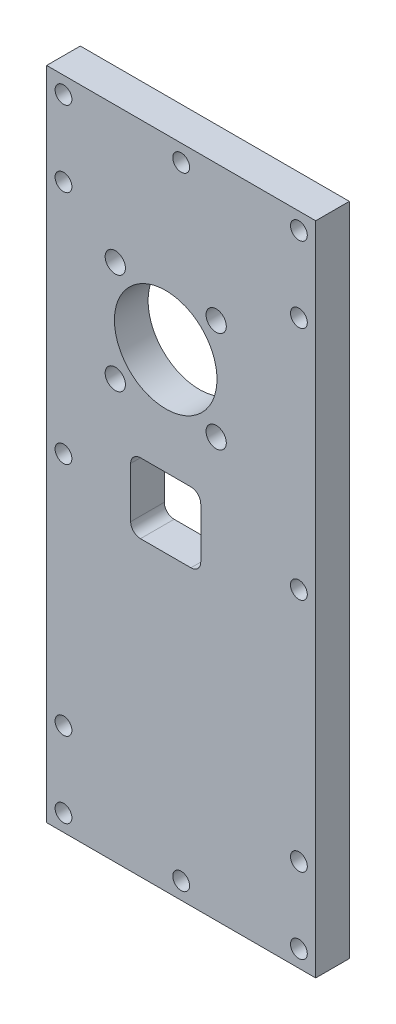
SolidWorks part; units mm, degrees
ref_plane "Ebene vorne" through (0, 0, 0) normal (0, 0, 1) x (1, 0, 0)
ref_plane "Ebene oben" through (0, 0, 0) normal (0, 1, 0) x (1, 0, 0)
ref_plane "Ebene rechts" through (0, 0, 0) normal (1, 0, 0) x (0, 0, -1)
sketch "Skizze1" plane through (0, 0, 0) normal (0, 0, 1) x (1, 0, 0)
  line L1 (-69.0594, 70.0995) -> (10.9406, 70.0995)
  line L2 (-69.0594, 70.0995) -> (-69.0594, -124.9005)
  line L3 (-69.0594, -124.9005) -> (10.9406, -124.9005)
  line L4 (10.9406, 70.0995) -> (10.9406, -124.9005)
  dimension "D1" = 195
  dimension "D2" = 80
extrude "Aufsatz-Linear austragen1" add sketch "Skizze1" against normal blind 10
sketch "Skizze2" plane through (0, 0, -10) normal (0, 0, -1) x (-1, 0, 0)
  line L0 (69.0594, 70.0995) -> (69.0594, -124.9005) construction
  line L1 (33.6594, 14.5995) -> (33.6594, -27.4005) construction
  line L3 (33.6594, 14.5995) -> (69.0594, 14.5995) construction
  line L5 (18.6594, 29.5995) -> (48.6594, 29.5995) construction
  line L6 (48.6594, 29.5995) -> (48.6594, -0.4005) construction
  line L7 (48.6594, -0.4005) -> (18.6594, -0.4005) construction
  line L8 (18.6594, -0.4005) -> (18.6594, 29.5995) construction
  line L9 (18.6594, 29.5995) -> (48.6594, -0.4005) construction
  line L10 (69.0594, -27.4005) -> (-10.9406, -27.4005) construction
  line L11 (-10.9406, -124.9005) -> (-10.9406, 70.0995) construction
  line L12 (23.2413, -19.9005) -> (23.2413, -34.9005)
  line L13 (26.1594, -16.9824) -> (41.1594, -16.9824)
  line L14 (44.0774, -19.9005) -> (44.0774, -34.9005)
  line L15 (41.1594, -37.8185) -> (26.1594, -37.8185)
  line L16 (23.2413, -19.9005) -> (44.0774, -34.9005) construction
  line L17 (26.1594, -37.8185) -> (41.1594, -16.9824) construction
  circle A0 centre (18.6594, 29.5995) radius 3.015
  circle A1 centre (48.6594, 29.5995) radius 3.015
  circle A2 centre (18.6594, -0.4005) radius 3.015
  circle A3 centre (48.6594, -0.4005) radius 3.015
  circle A4 centre (33.6594, 14.5995) radius 15.25
  arc A5 (23.2413, -19.9005) -> (26.1594, -16.9824) centre (26.1594, -19.9005) cw
  arc A6 (41.1594, -16.9824) -> (44.0774, -19.9005) centre (41.1594, -19.9005) cw
  arc A7 (44.0774, -34.9005) -> (41.1594, -37.8185) centre (41.1594, -34.9005) cw
  arc A8 (26.1594, -37.8185) -> (23.2413, -34.9005) centre (26.1594, -34.9005) cw
  point P22 (33.6594, 14.5995)
  point P32 (33.6594, -27.4005)
  dimension "D1" = 30
  dimension "D3" = 6.03
  dimension "D2" = 30
  dimension "D4" = 35.4
  dimension "D5" = 42
  dimension "D6" = 15
extrude "Schnitt-Linear austragen1" cut sketch "Skizze2" against normal blind 10
sketch "Skizze3" plane through (0, 0, -10) normal (0, 0, -1) x (-1, 0, 0)
  line L0 (-5.9406, 65.0995) -> (63.8159, 65.0995) construction
  line L1 (63.8159, 65.0995) -> (63.8159, 42.5995) construction
  line L2 (63.8159, 42.5995) -> (63.8159, -27.4005) construction
  line L4 (63.8159, -27.4005) -> (63.8159, -97.4005) construction
  line L5 (63.8159, -97.4005) -> (63.8159, -119.9005) construction
  line L6 (63.8159, -119.9005) -> (-5.9406, -119.9005) construction
  line L7 (-5.9406, -119.9005) -> (-5.9406, -97.4005) construction
  line L8 (-5.9406, -97.4005) -> (-5.9406, -27.4005) construction
  line L10 (-5.9406, -27.4005) -> (-5.9406, 42.5995) construction
  line L11 (-5.9406, 42.5995) -> (-5.9406, 65.0995) construction
  line L12 (28.9377, 65.0995) -> (29.0594, 70.0995) construction
  line L13 (-10.9406, 70.0995) -> (69.0594, 70.0995) construction
  line L14 (28.9377, -119.9005) -> (29.0594, -124.9005) construction
  line L15 (69.0594, -124.9005) -> (-10.9406, -124.9005) construction
  line L16 (-10.9406, -124.9005) -> (-10.9406, 70.0995) construction
  circle A0 centre (-5.9406, 65.0995) radius 1.25
  circle A1 centre (63.8159, 65.0995) radius 1.25
  circle A2 centre (28.9377, 65.0995) radius 1.25
  circle A3 centre (63.8159, 42.5995) radius 1.25
  circle A5 centre (63.8159, -27.4005) radius 1.25
  circle A6 centre (63.8159, -97.4005) radius 1.25
  circle A7 centre (63.8159, -119.9005) radius 1.25
  circle A8 centre (28.9377, -119.9005) radius 1.25
  circle A9 centre (-5.9406, -119.9005) radius 1.25
  circle A10 centre (-5.9406, -97.4005) radius 1.25
  circle A11 centre (-5.9406, -27.4005) radius 1.25
  circle A13 centre (-5.9406, 42.5995) radius 1.25
  point P26 (-5.9406, -26.6299)
  dimension "D4" = 2.5
  dimension "D1" = 5
  dimension "D2" = 5
  dimension "D3" = 5
  dimension "D5" = 70
extrude "Schnitt-Linear austragen2" cut sketch "Skizze3" against normal blind 5
sketch "Skizze4" plane through (0, 0, 0) normal (0, 0, 1) x (1, 0, 0)
  line L0 (-64.0594, 65.0995) -> (-64.0594, 42.5995) construction
  line L1 (-64.0594, 42.5995) -> (-64.0594, -27.4005) construction
  line L2 (-64.0594, -27.4005) -> (-64.0594, -97.4005) construction
  line L3 (-64.0594, -97.4005) -> (-64.0594, -119.9005) construction
  line L4 (5.9406, 65.0995) -> (5.9406, 42.5995) construction
  line L5 (5.9406, -119.9005) -> (-64.0594, -119.9005) construction
  line L6 (5.9406, 42.5995) -> (5.9406, -27.4005) construction
  line L7 (5.9406, -27.4005) -> (5.9406, -97.4005) construction
  line L8 (5.9406, -97.4005) -> (5.9406, -119.9005) construction
  line L11 (-64.0594, 65.0995) -> (5.9406, 65.0995) construction
  line L12 (-29.0594, 65.0995) -> (-29.0594, 70.0995) construction
  line L13 (10.9406, 70.0995) -> (-69.0594, 70.0995) construction
  line L15 (-69.0594, -124.9005) -> (10.9406, -124.9005) construction
  circle A0 centre (-64.0594, 65.0995) radius 2.5
  circle A1 centre (5.9406, 65.0995) radius 2.5
  circle A2 centre (5.9406, 42.5995) radius 2.5
  circle A3 centre (5.9406, -27.4005) radius 2.5
  circle A5 centre (5.9406, -97.4005) radius 2.5
  circle A6 centre (5.9406, -119.9005) radius 2.5
  circle A7 centre (-64.0594, -119.9005) radius 2.5
  circle A8 centre (-64.0594, -97.4005) radius 2.5
  circle A10 centre (-64.0594, -27.4005) radius 2.5
  circle A11 centre (-64.0594, 42.5995) radius 2.5
  circle A12 centre (-29.0594, -119.9005) radius 2.5
  circle A13 centre (-29.0594, 65.0995) radius 2.5
  dimension "D4" = 5
  dimension "D1" = 70
  dimension "D2" = 5
  dimension "D3" = 5
extrude "Schnitt-Linear austragen3" cut sketch "Skizze4" against normal blind 5
